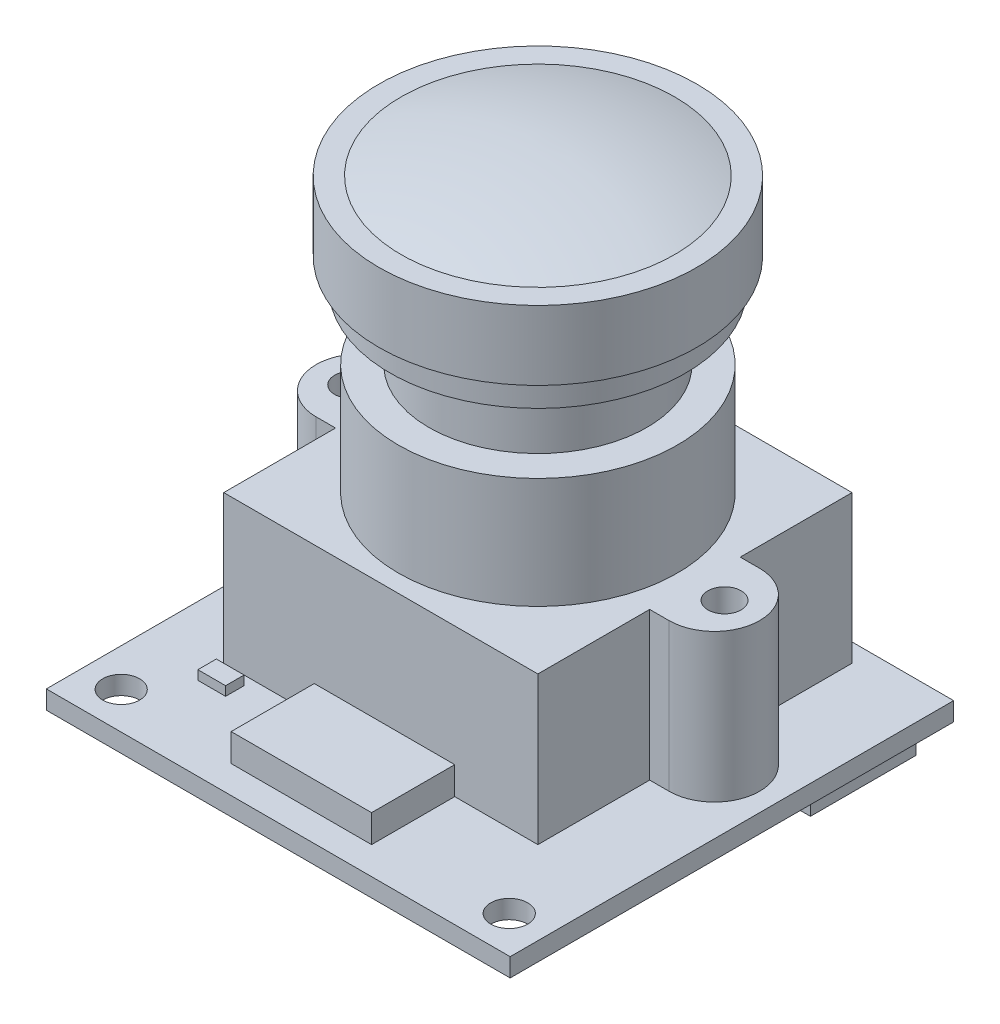
SolidWorks part; units mm, degrees
ref_plane "Front Plane" through (0, 0, 0) normal (0, 0, 1) x (1, 0, 0)
ref_plane "Top Plane" through (0, 0, 0) normal (0, 1, 0) x (1, 0, 0)
ref_plane "Right Plane" through (0, 0, 0) normal (1, 0, 0) x (0, 0, -1)
sketch "Sketch1" plane through (0, 0, 0) normal (1, 0, 0) x (0, 0, -1)
  line L0 (0, 0) -> (0, 30.3805) construction
  line L1 (0, 0) -> (0, 16)
  line L2 (7.4, 14.85) -> (8.6, 14.85)
  line L3 (8.6, 14.85) -> (8.6, 11.1)
  line L4 (8.6, 11.1) -> (8, 11.1)
  line L5 (8, 11.1) -> (8, 9.6)
  line L6 (8, 9.6) -> (5.9, 9.6)
  line L7 (5.9, 9.6) -> (5.9, 6)
  line L8 (5.9, 6) -> (7.55, 6)
  line L9 (7.55, 6) -> (7.55, 0)
  line L10 (7.55, 0) -> (0, 0)
  line L11 (0, 16) -> (-17.9797, 16) construction
  arc A0 (0, 16) -> (7.4, 14.85) centre (0, -8.3837) cw
  dimension "D1" = 7.55
  dimension "D2" = 6
  dimension "D3" = 5.9
  dimension "D4" = 8
  dimension "D5" = 3.75
  dimension "D6" = 8.6
  dimension "D7" = 3.6
  dimension "D8" = 1.5
  dimension "D9" = 16
  dimension "D10" = 1.2
revolve "Revolve1" add sketch "Sketch1" angle 360 about L0
sketch "Sketch2" plane through (0, 0, 0) normal (0, -1, 0) x (1, 0, 0)
  line L0 (0, 0) -> (9.55, 0) construction
  line L1 (-8.5, -8.5) -> (8.5, -8.5)
  line L2 (-8.5, -8.5) -> (-8.5, -2.45)
  line L3 (-8.5, 8.5) -> (8.5, 8.5)
  line L4 (8.5, -8.5) -> (8.5, -2.45)
  line L5 (-8.5, -8.5) -> (8.5, 8.5) construction
  line L6 (-8.5, 8.5) -> (8.5, -8.5) construction
  line L7 (0, 0) -> (-9.55, 0) construction
  line L8 (-9.55, 2.45) -> (-8.5, 2.45)
  line L9 (-9.55, -2.45) -> (-8.5, -2.45)
  line L10 (9.55, -2.45) -> (8.5, -2.45)
  line L11 (9.55, 2.45) -> (8.5, 2.45)
  line L12 (-9.55, 0) -> (-12, 0) construction
  line L13 (9.55, 0) -> (12, 0) construction
  line L14 (-10.1, 0) -> (0, -8.5) construction
  line L15 (0, -8.5) -> (10.1, 0) construction
  line L16 (8.5, 2.45) -> (8.5, 8.5)
  line L18 (-8.5, 2.45) -> (-8.5, 8.5)
  circle A0 centre (-10.1, 0) radius 0.9
  circle A1 centre (10.1, 0) radius 0.9
  arc A4 (-9.55, 2.45) -> (-9.55, -2.45) centre (-9.55, 0) ccw
  arc A5 (9.55, -2.45) -> (9.55, 2.45) centre (9.55, 0) ccw
  point P0 (0, 0)
  dimension "D3" = 24
  dimension "D4" = 4.9
  dimension "D6" = 22
  dimension "D5" = 1.8
  dimension "D1" = 17
  dimension "D2" = 17
extrude "Boss-Extrude1" add sketch "Sketch2" along normal blind 8
sketch "Sketch3" plane through (0, 0, -8.5) normal (0, 0, -1) x (-1, 0, 0)
  line L0 (8.5, 0) -> (-8.5, 0) construction
  line L1 (-1.25, 0) -> (1.25, 0)
  line L2 (-1.25, 0) -> (-1.25, 6)
  line L3 (-1.25, 6) -> (1.25, 6)
  line L4 (1.25, 0) -> (1.25, 6)
  line L5 (7.55, 6) -> (-7.55, 6) construction
  line L6 (0, 0) -> (0, 6) construction
  dimension "D1" = 2.5
extrude "Boss-Extrude2" add sketch "Sketch3" against normal up to surface (1.0542 mm away) up to face at (0, 6, -7.55)
sketch "Sketch4" plane through (0, 0, -8.5) normal (0, 0, -1) x (-1, 0, 0)
  line L0 (0, 0) -> (0, 6) construction
  line L1 (1.25, 6) -> (-1.25, 6) construction
  circle A0 centre (0, 3.75) radius 0.5
  dimension "D1" = 1
  dimension "D2" = 3.75
extrude "Cut-Extrude1" cut sketch "Sketch4" against normal blind 8
sketch "Sketch5" plane through (0, -8, 0) normal (0, -1, 0) x (1, 0, 0)
  line L0 (-8.5, -8.5) -> (8.5, -8.5) construction
  line L1 (13, -9.5) -> (-12.1, -9.5)
  line L2 (13, -9.5) -> (13, 14.5)
  line L3 (13, 14.5) -> (-12.1, 14.5)
  line L4 (-12.1, -9.5) -> (-12.1, 14.5)
  line L5 (8.5, 8.5) -> (-8.5, 8.5) construction
  line L6 (0, 0) -> (0, 21.7665) construction
  line L7 (8.5, 2.45) -> (8.5, 8.5) construction
  line L8 (-8.5, 8.5) -> (-8.5, 2.45) construction
  dimension "D1" = 1
  dimension "D2" = 6
  dimension "D3" = 24
  dimension "D4" = 25.1
  dimension "D5" = 4.5
  dimension "D6" = 3.6
extrude "Boss-Extrude3" add sketch "Sketch5" along normal blind 1
sketch "Sketch6" plane through (0, -8, 0) normal (0, 1, 0) x (1, 0, 0)
  line L0 (0, -8.6) -> (0, -15.9592) construction
  line L1 (8.5, -8.5) -> (-8.5, -8.5) construction
  line L2 (-3.6, -8.5) -> (4, -8.5)
  line L3 (-3.6, -8.5) -> (-3.6, -13)
  line L4 (-3.6, -13) -> (4, -13)
  line L5 (4, -8.5) -> (4, -13)
  line L6 (13, -14.5) -> (-12.1, -14.5) construction
  line L7 (-12.1, -14.5) -> (-12.1, 9.5) construction
  circle A0 centre (0, 0) radius 8.6 construction
  dimension "D1" = 1.5
  dimension "D2" = 7.6
  dimension "D3" = 8.5
extrude "Boss-Extrude4" add sketch "Sketch6" along normal blind 1.5
sketch "Sketch7" plane through (0, -8, 0) normal (0, 1, 0) x (1, 0, 0)
  line L0 (-10.05, -12.5) -> (10.95, -12.5) construction
  line L1 (-12.1, -14.5) -> (-12.1, 9.5) construction
  line L2 (13, 9.5) -> (13, -14.5) construction
  line L3 (13, -14.5) -> (-12.1, -14.5) construction
  circle A0 centre (-10.05, -12.5) radius 1
  circle A1 centre (10.95, -12.5) radius 1
  dimension "D1" = 23
  dimension "D2" = 2
  dimension "D3" = 1.05
  dimension "D4" = 1.05
  dimension "D5" = 1
extrude "Cut-Extrude2" cut sketch "Sketch7" against normal through all
sketch "Sketch8" plane through (0, -8, 0) normal (0, 1, 0) x (1, 0, 0)
  line L0 (13, -14.5) -> (-12.1, -14.5) construction
  line L1 (-8.4, -9) -> (-6.9, -9)
  line L2 (-8.4, -9) -> (-8.4, -10)
  line L3 (-8.4, -10) -> (-6.9, -10)
  line L4 (-6.9, -9) -> (-6.9, -10)
  line L5 (-12.1, -14.5) -> (-12.1, 9.5) construction
  dimension "D1" = 1.5
  dimension "D2" = 1
  dimension "D3" = 4.5
  dimension "D4" = 3.7
extrude "Boss-Extrude5" add sketch "Sketch8" along normal blind 0.5
sketch "Sketch9" plane through (0, -9, 0) normal (0, -1, 0) x (1, 0, 0)
  line L0 (-12.1, -9.5) -> (13, -9.5) construction
  line L1 (-10.05, -9.5) -> (10.95, -9.5)
  line L2 (-10.05, -9.5) -> (-10.05, -3.8)
  line L3 (-10.05, -3.8) -> (10.95, -3.8)
  line L4 (10.95, -9.5) -> (10.95, -3.8)
  line L5 (0.45, 14.5) -> (0.45, -3.8) construction
  line L6 (13, 14.5) -> (-12.1, 14.5) construction
  dimension "D1" = 5.7
  dimension "D2" = 21
extrude "Boss-Extrude6" add sketch "Sketch9" along normal blind 2.6
